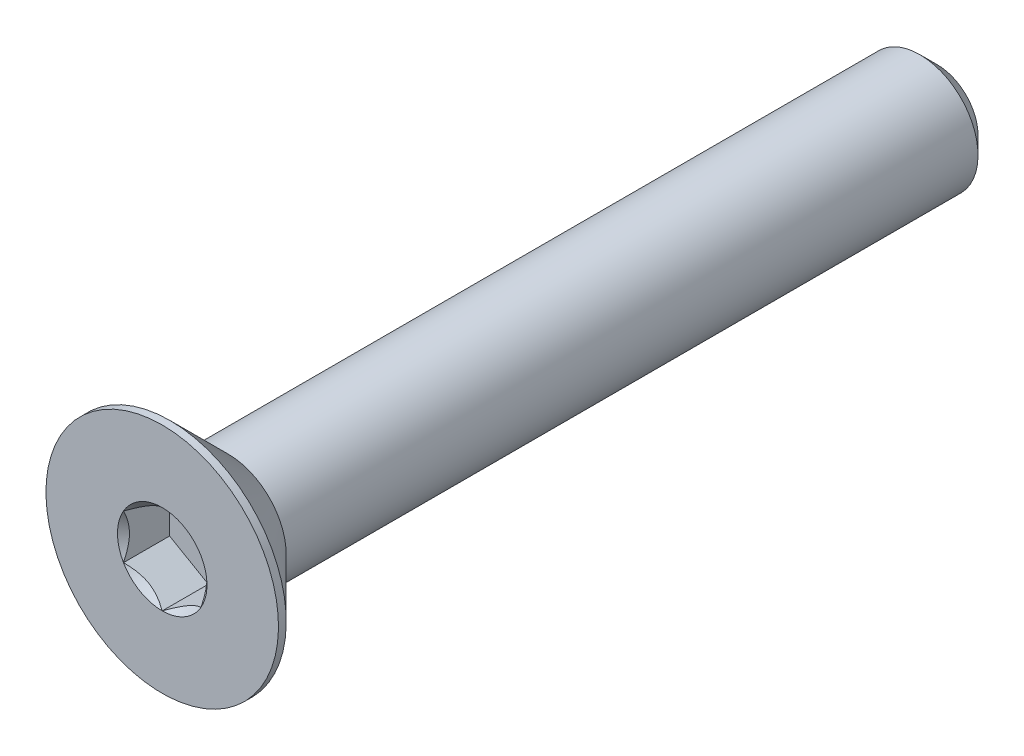
SolidWorks part; units mm, degrees
material "Alloy Steel"
ref_plane "Front" through (0, 0, 0) normal (0, 0, 1) x (1, 0, 0)
ref_plane "Top" through (0, 0, 0) normal (0, 1, 0) x (1, 0, 0)
ref_plane "Right" through (0, 0, 0) normal (1, 0, 0) x (0, 0, -1)
ref_axis "Central Axis" through (0, 0, -89.2244) along (0, 0, 1)
sketch "Sketch1" plane through (0, 0, 0) normal (1, 0, 0) x (0, 0, -1)
  line L0 (-10, 3) -> (-9.8, 3) construction
  line L1 (-9.8, 3) -> (-8.3, 1.5) construction
  line L2 (-10, 1.5) -> (10, 1.5) construction
  line L3 (10, 1.5) -> (10, 0) construction
  line L4 (10, 0) -> (-10, 0) construction
  line L5 (-10, 0) -> (-10, 3) construction
  line L6 (-10, 3) -> (-10, -3) construction
  line L7 (10, 1.5) -> (10, -1.5) construction
  line L8 (-10, -3) -> (-9.8, -3) construction
  line L9 (-9.8, -3) -> (-8.3, -1.5) construction
  line L11 (-10, 1.5) -> (-10, 0) construction
  line L12 (-8.3, 1.5) -> (-8.3, 0) construction
  line L13 (9.9688, 1.5541) -> (10.2188, 1.1211) construction
  line L14 (10.2188, 1.1211) -> (10.4688, 1.5541) construction
  line L15 (10.4688, 1.5541) -> (9.9688, 1.5541) construction
  line L16 (10.2188, 1.5541) -> (10.2188, 1.5) construction
  line L17 (10.2188, 1.5) -> (10.2188, 1.1752) construction
  line L18 (10.2188, 1.1752) -> (10.2188, 1.1211) construction
  line L19 (10.2188, 1.5271) -> (10.4531, 1.5271) construction
  line L20 (10.2188, 1.5271) -> (9.9844, 1.5271) construction
  line L21 (10, 1.5) -> (10.4375, 1.5) construction
  line L22 (10.1875, 1.1752) -> (10.25, 1.1752) construction
  line L23 (10, -1.5) -> (-8.3, -1.5) construction
  point P10 (8.75, -1.5)
  point P24 (-8.3, 1.5)
  point P30 (0, 0)
  dimension "Head Diameter" = 6
  dimension "Head Height" = 1.7
  dimension "Length" = 20
  dimension "Countersink Angle" = 90
  dimension "Thread Pitch" = 0.5
  dimension "D2" = 0.0625
  dimension "Minimum Thread Length" = 18.3
  dimension "Thread Size" = 3
  dimension "D1" = 1.25
sketch "Sketch2" plane through (0, 0, 0) normal (0, 0, 1) x (1, 0, 0)
  line L1 (0, 1.1547) -> (-1, 0.5774) construction
  line L2 (-1, 0.5774) -> (-1, -0.5774) construction
  line L3 (-1, -0.5774) -> (0, -1.1547) construction
  line L4 (0, -1.1547) -> (1, -0.5774) construction
  line L5 (1, -0.5774) -> (1, 0.5774) construction
  line L6 (1, 0.5774) -> (0, 1.1547) construction
  circle A0 centre (0, 0) radius 1 construction
  dimension "Drive Size" = 2
sketch "Sketch3" plane through (0, 0, 0) normal (1, 0, 0) x (0, 0, -1)
  line L0 (-10, 1.5) -> (10, 1.5)
  line L1 (10, 1.5) -> (10, 0)
  line L2 (10, 0) -> (-10, 0)
  line L3 (-10, 0) -> (-10, 1.5)
revolve "Revolve1" add sketch "Sketch3" angle 360 about L4
chamfer "Chamfer1" distance 0.45 angle 45 1 edges at (0, 1.5, -10)
sketch "Sketch6" plane through (0, 0, 0) normal (1, 0, 0) x (0, 0, -1)
  line L0 (-10, 3) -> (-9.8, 3)
  line L1 (-9.8, 3) -> (-8.3, 1.5)
  line L2 (-8.3, 1.5) -> (-8.3, 0)
  line L3 (-8.3, 0) -> (-10, 0)
  line L4 (-10, 0) -> (-10, 3)
revolve "Revolve2" add sketch "Sketch6" angle 360 about L4
sketch "Sketch8" plane through (0, 0, 10) normal (0, 0, 1) x (1, 0, 0)
  line L0 (0, 1.1547) -> (-1, 0.5774) construction
  line L1 (1, 0.5774) -> (0, 1.1547) construction
  line L2 (1, -0.5774) -> (1, 0.5774) construction
  line L3 (0, -1.1547) -> (1, -0.5774) construction
  line L4 (-1, 0.5774) -> (-1, -0.5774) construction
  line L5 (-1, -0.5774) -> (0, -1.1547) construction
  line L6 (0, 1.1547) -> (-1, 0.5774)
  line L7 (1, 0.5774) -> (0, 1.1547)
  line L8 (1, -0.5774) -> (1, 0.5774)
  line L9 (0, -1.1547) -> (1, -0.5774)
  line L10 (-1, 0.5774) -> (-1, -0.5774)
  line L11 (-1, -0.5774) -> (0, -1.1547)
extrude "Cut-Extrude1" cut sketch "Sketch8" against normal blind 1.19
sketch "Sketch9" plane through (0, 0, 10) normal (0, 0, 1) x (1, 0, 0)
  circle A0 centre (0, 0) radius 1.1547
extrude "Cut-Extrude2" cut sketch "Sketch9" against normal up to next (1.19 mm away) draft 45
ref_plane "Plane1" [suppressed] through (0, 0, 8.3) normal (0, 0, 1) x (1, 0, 0)
split "Split1" [suppressed] bodies to split 124
sketch "Sketch4" [suppressed] plane through (0, 0, -10) normal (0, 0, -1) x (-1, 0, 0)
  circle A0 centre (0, 0) radius 1.5 construction
  circle A1 centre (0, 0) radius 1.5
curve "Helix/Spiral1" [suppressed] pitch 0.5 height 18.8 turns 37.6
sketch "Sketch10" [suppressed] plane through (0, 0, 0) normal (1, 0, 0) x (0, 0, -1)
  line L0 (9.9844, 1.5271) -> (10.4531, 1.5271)
  line L1 (10.4531, 1.5271) -> (10.25, 1.1752)
  line L2 (10.25, 1.1752) -> (10.1875, 1.1752)
  line L3 (10.1875, 1.1752) -> (9.9844, 1.5271)
sweep "Cut-Sweep1" [suppressed] cut profiles "Sketch10" path "Helix/Spiral1"
equation "\"D2@Sketch1\" = \"Thread Pitch@Sketch1\" / 8"
equation "\"D4@Helix/Spiral1\"=\"Thread Pitch@Sketch1\""
equation "\"D3@Helix/Spiral1\"=\"Minimum Thread Length@Sketch1\"+\"Thread Pitch@Sketch1\""
equation "\"D1@Chamfer1\"=\"Thread Size@Sketch1\"*.15"
equation "\"D1@Cut-Extrude1\"=\"Head Height@Sketch1\"*.7"
equation "\"D1@Sketch1\"=\"Thread Pitch@Sketch1\"*2.5"
